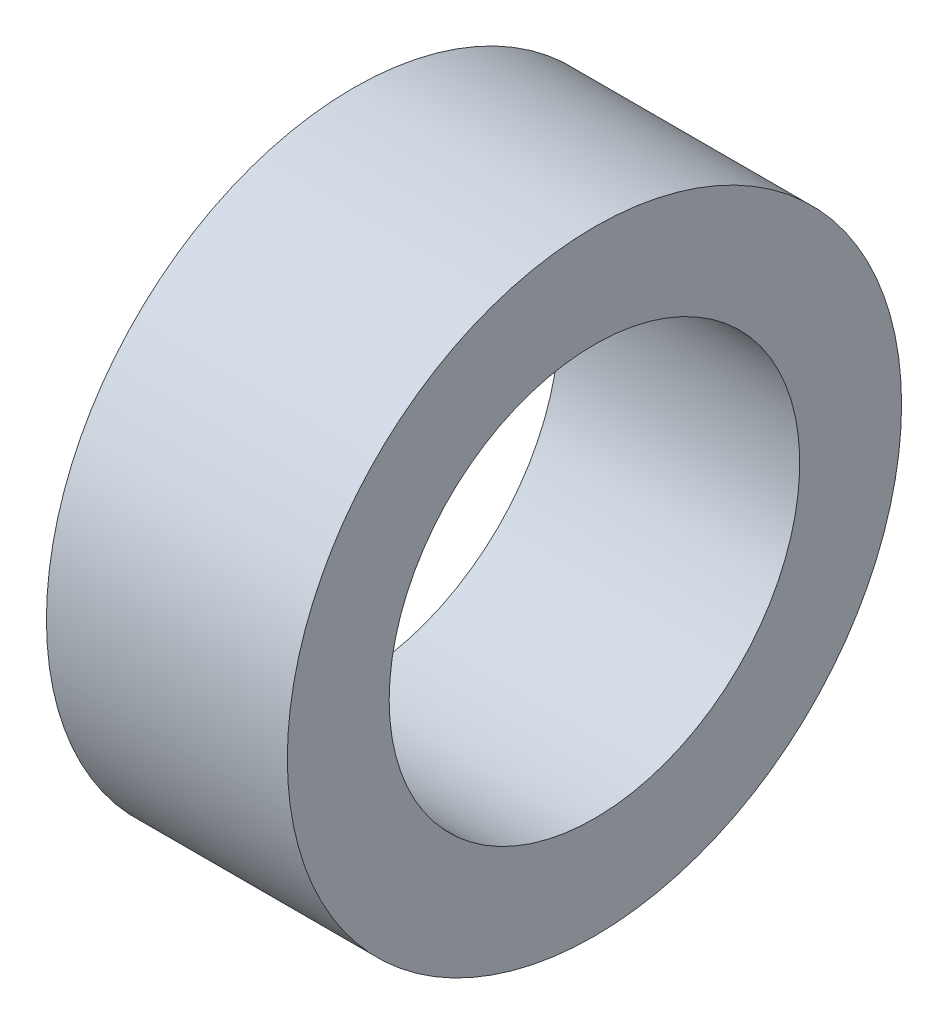
SolidWorks part; units mm, degrees
material "6061-T6 (SS)"
ref_plane "Front Plane" through (0, 0, 0) normal (0, 0, 1) x (1, 0, 0)
ref_plane "Top Plane" through (0, 0, 0) normal (0, 1, 0) x (1, 0, 0)
ref_plane "Right Plane" through (0, 0, 0) normal (1, 0, 0) x (0, 0, -1)
sketch "Sketch1" plane through (0, 0, 0) normal (0, 0, 1) x (1, 0, 0)
  line L1 (30.5156, 6.1277) -> (35.3219, 6.1277)
  line L2 (30.5156, 6.1277) -> (30.5156, 4.0957)
  line L3 (30.5156, 4.0957) -> (35.3219, 4.0957)
  line L4 (35.3219, 6.1277) -> (35.3219, 4.0957)
  line L5 (0, 0) -> (42.6651, 0) construction
  line L6 (30.5156, -12.3825) -> (30.5156, 12.3825) construction
  line L8 (35.3219, 46.2794) -> (35.3219, 10.4991) construction
  dimension "D1" = 8.1915
  dimension "D2" = 2.032
revolve "Revolve1" add sketch "Sketch1" angle 360 about L5
equation "\"D1@Sketch1\"=5/16+0.01"
